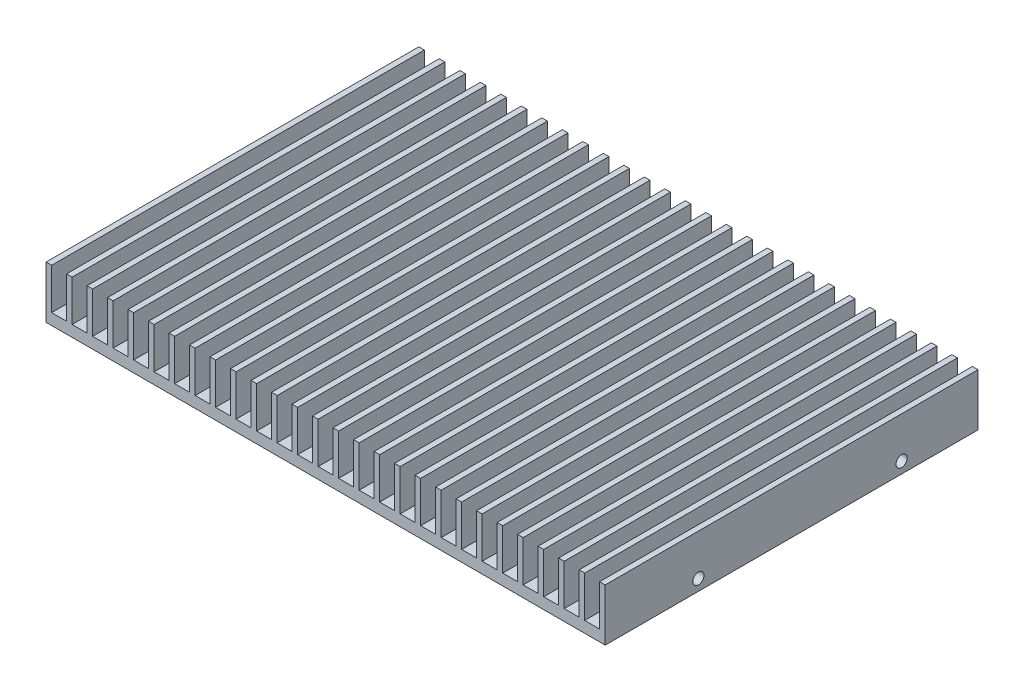
SolidWorks part; units mm, degrees
ref_plane "Спереди" through (0, 0, 0) normal (0, 0, 1) x (1, 0, 0)
ref_plane "Сверху" through (0, 0, 0) normal (0, 1, 0) x (1, 0, 0)
ref_plane "Справа" through (0, 0, 0) normal (1, 0, 0) x (0, 0, -1)
sketch "Эскиз2" plane through (0, 0, 0) normal (0, 1, 0) x (1, 0, 0)
  line L1 (-75, -50) -> (75, -50)
  line L2 (-75, -50) -> (-75, 50)
  line L3 (-75, 50) -> (75, 50)
  line L4 (75, -50) -> (75, 50)
  point P0 (0, 0)
  dimension "D1" = 100
extrude "Бобышка-Вытянуть1" add sketch "Эскиз2" along normal blind 3
sketch "Эскиз3" plane through (0, 3, 0) normal (0, 1, 0) x (1, 0, 0)
  line L0 (-75, -50) -> (75, -50) construction
  line L1 (-75, 50) -> (-73.5, 50)
  line L2 (-75, 50) -> (-75, -50)
  line L3 (-75, -50) -> (-73.5, -50)
  line L4 (-73.5, 50) -> (-73.5, -50)
extrude "Бобышка-Вытянуть2" add sketch "Эскиз3" along normal blind 11
pattern_linear "Линейный массив1" count 28 spacing 5.5 along (1, 0, 0) of "Бобышка-Вытянуть2"
sketch "Эскиз4" plane through (75, 0, 0) normal (1, 0, 0) x (0, 0, -1)
  circle A1 centre (29.5, 3) radius 1.55
sketch "Эскиз5" plane through (75, 0, 0) normal (1, 0, 0) x (0, 0, -1)
  circle A0 centre (-25, 3) radius 1.55
sketch "Эскиз23" plane through (75, 0, 0) normal (1, 0, 0) x (0, 0, -1)
  point P0 (29.5, 3)
  point P3 (-25, 3)
hole_wizard "Отверстие обработанное метчиком M4x0.51" positions "Эскиз23" profile "Эскиз24" tap size "M4x0.5" standard "DIN"
sketch "Эскиз24" plane through (75, 3, -29.5) normal (0, 1, 0) x (0, 0, -1)
  line L0 (0, 0) -> (0, 6)
  line L1 (0, 6) -> (1.5, 5.0987)
  line L2 (1.5, 5.0987) -> (1.5, 0)
  line L5 (1.5, 0) -> (0, 0)
  line L10 (0, 6) -> (-1.5, 5.0987) construction
  line L11 (0, -6.35) -> (0, 107.95) construction
  dimension "Диаметр сверла" = 3
  dimension "Глубина сверла" = 6
  dimension "Угол заточки сверла" = 118
cosmetic thread "Отверстие резьбы1" parameters "D1"=5.5, "D2"=4
cosmetic thread "Отверстие резьбы2" parameters "D1"=5.5, "D2"=4
mirror "Зеркальное отражение1" about plane through (0, 0, 0) normal (1, 0, 0) of "Отверстие обработанное метчиком M4x0.51"
sketch "Эскиз27" plane through (0, 0, 0) normal (0, -1, 0) x (1, 0, 0)
  circle A1 centre (52.825, -39.3) radius 1.55
extrude "Вырез-Вытянуть1" cut sketch "Эскиз27" against normal blind 3
sketch "Эскиз28" plane through (0, 0, 0) normal (0, -1, 0) x (1, 0, 0)
  circle A0 centre (39.6, -36) radius 1.55
extrude "Вырез-Вытянуть2" cut sketch "Эскиз28" against normal blind 3
pattern_linear "Линейный массив2" count 8 spacing 11.5 along (-1, 0, 0) of "Вырез-Вытянуть2"
sketch "Эскиз29" plane through (0, 0, 0) normal (0, -1, 0) x (-1, 0, 0)
  line L0 (-53, 37.7599) -> (-53, 40.8401) construction
  point P0 (-53, 39.3)
  point P4 (-39.6, 36)
  point P7 (-28.1, 36)
  point P10 (-16.6, 36)
  point P13 (-5.1, 36)
  point P16 (6.4, 36)
  point P19 (17.9, 36)
  point P22 (40.9, 36)
  point P25 (29.4, 36)
hole_wizard "Отверстие обработанное метчиком M3x0.51" positions "Эскиз29" profile "Эскиз30" tap size "M3x0.5" standard "Ansi Metric"
sketch "Эскиз30" plane through (53, 0, -39.3) normal (1, 0, 0) x (0, 0, -1)
  line L0 (0, 0) -> (0, 6.2511)
  line L1 (0, 6.2511) -> (1.25, 5.5)
  line L2 (1.25, 5.5) -> (1.25, 0.275)
  line L3 (1.25, 0.275) -> (1.525, 0)
  line L5 (1.525, 0) -> (0, 0)
  line L6 (-1.25, 0.275) -> (-1.525, 0) construction
  line L10 (0, 6.2511) -> (-1.25, 5.5) construction
  line L11 (0, -6.35) -> (0, 107.95) construction
  dimension "Диаметр сверла" = 2.5
  dimension "Глубина сверла" = 5.5
  dimension "Диаметр передней зенковки" = 3.05
  dimension "Угол передней зенковки" = 90
  dimension "Угол заточки сверла" = 118
